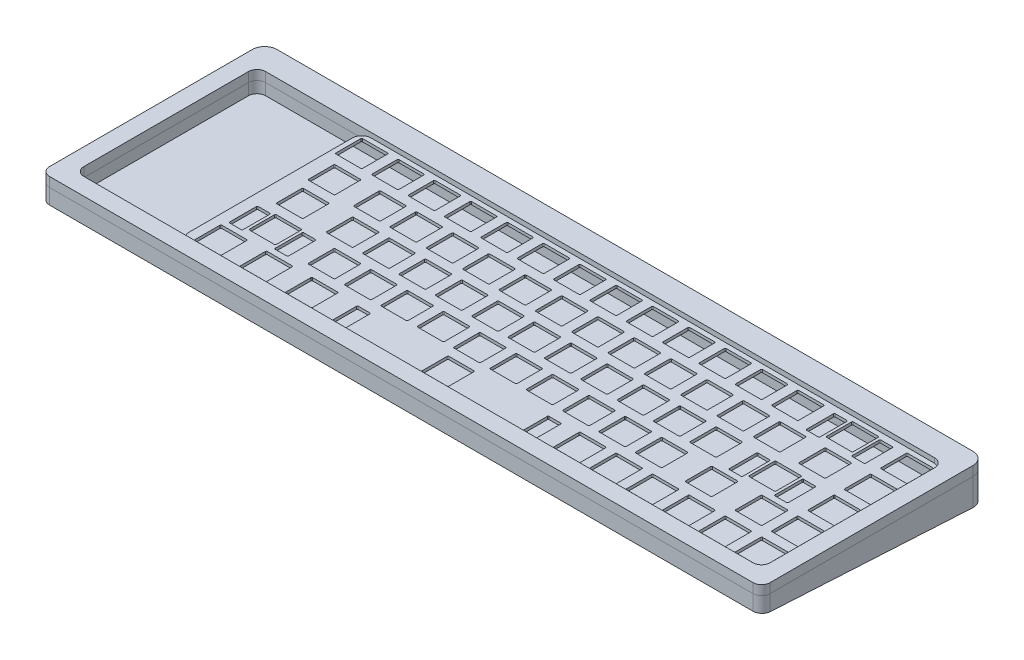
SolidWorks part; units mm, degrees
other "PCB"
other "Plate"
other "Bottom"
other "Top"
ref_plane "Front Plane" through (0, 0, 0) normal (0, 0, 1) x (1, 0, 0)
ref_plane "Top Plane" through (0, 0, 0) normal (0, 1, 0) x (1, 0, 0)
ref_plane "Right Plane" through (0, 0, 0) normal (1, 0, 0) x (0, 0, -1)
sketch "Sketch1" plane through (0, 0, 0) normal (0, 1, 0) x (1, 0, 0)
  line L0 (-179.825, 47.6224) -> (-179.825, 47.625)
  line L1 (-179.8217, 47.625) -> (179.825, 47.625)
  line L2 (-179.825, 47.6224) -> (-179.825, -47.625)
  line L3 (-179.825, -47.625) -> (179.825, -47.625)
  line L4 (179.825, 47.625) -> (179.825, -47.625)
  line L5 (-179.825, 47.625) -> (179.825, -47.625) construction
  line L6 (-179.825, -47.625) -> (179.825, 47.625) construction
  line L7 (-179.825, 47.625) -> (-179.8217, 47.625)
  circle A4 centre (157.075, 19.175) radius 1.1
  circle A5 centre (136.925, -16.775) radius 1.1
  circle A6 centre (-153.475, 33.725) radius 1.1
  circle A7 centre (17.925, 22.275) radius 1.1
  circle A8 centre (17.875, -35.075) radius 1.1
  circle A9 centre (-130.375, -35.725) radius 1.1
  point P0 (0, 0)
  dimension "D4" = 2.2
  dimension "D7" = 2.2
  dimension "D8" = 2.2
  dimension "D9" = 2.2
  dimension "D10" = 2.2
  dimension "D11" = 2.2
  dimension "D1" = 359.65
  dimension "D2" = 95.25
  dimension "D5" = 22.75
  dimension "D6" = 28.45
  dimension "D12" = 42.9
  dimension "D13" = 30.85
  dimension "D14" = 25.35
  dimension "D15" = 161.9
  dimension "D16" = 12.55
  dimension "D17" = 161.95
  dimension "D18" = 11.9
  dimension "D19" = 49.45
  dimension "D20" = 13.9
  dimension "D21" = 26.35
sketch "Sketch2" plane through (0, 0, 0) normal (0, 1, 0) x (1, 0, 0)
  line L0 (-188.825, 54.625) -> (-188.825, 60.625)
  line L1 (-188.825, 60.625) -> (-182.825, 60.625)
  line L4 (-179.825, 46.625) -> (-179.825, -46.625)
  line L5 (-178.825, -47.625) -> (178.825, -47.625)
  line L6 (179.825, 46.625) -> (179.825, -46.625)
  line L7 (-178.825, 47.625) -> (178.825, 47.625)
  line L8 (-179.825, 46.625) -> (-179.825, 47.625)
  line L9 (-182.825, 60.625) -> (188.825, 60.625)
  line L10 (-188.825, 54.625) -> (-188.825, -56.625)
  line L11 (-188.825, -56.625) -> (188.825, -56.625)
  line L12 (188.825, 60.625) -> (188.825, -56.625)
  line L13 (-179.825, 47.625) -> (-178.825, 47.625)
  line L14 (-179.825, -46.625) -> (-179.825, -47.625)
  line L15 (-179.825, -47.625) -> (-178.825, -47.625)
  line L16 (178.825, -47.625) -> (179.825, -47.625)
  line L17 (179.825, -47.625) -> (179.825, -46.625)
  line L18 (178.825, 47.625) -> (179.825, 47.625)
  line L19 (179.825, 47.625) -> (179.825, 46.625)
  circle A0 centre (157.075, 19.175) radius 1.1 construction
  circle A1 centre (136.925, -16.775) radius 1.1 construction
  circle A2 centre (17.875, -35.075) radius 1.1 construction
  circle A3 centre (17.925, 22.275) radius 1.1 construction
  circle A4 centre (-153.475, 33.725) radius 1.1 construction
  circle A5 centre (-130.375, -35.725) radius 1.1 construction
  circle A10 centre (157.075, 19.175) radius 1.1
  circle A11 centre (136.925, -16.775) radius 1.1
  circle A12 centre (17.875, -35.075) radius 1.1
  circle A13 centre (17.925, 22.275) radius 1.1
  circle A14 centre (-153.475, 33.725) radius 1.1
  circle A15 centre (-130.375, -35.725) radius 1.1
  point P30 (0, 0)
  dimension "D1" = 13
  dimension "D2" = 9
  dimension "D3" = 9
  dimension "D4" = 9
extrude "Boss-Extrude1" add sketch "Sketch2" along normal blind 13
sketch "Sketch4" plane through (0, 0, 0) normal (0, -1, 0) x (1, 0, 0)
  line L1 (-188.825, -60.625) -> (188.825, -60.625) construction
  line L3 (-188.825, 56.625) -> (188.825, 56.625) construction
  line L4 (-179.825, 47.625) -> (-179.825, -47.625)
  line L5 (179.825, 47.625) -> (-179.825, 47.625)
  line L6 (179.825, -47.625) -> (179.825, 47.625)
  line L7 (-179.825, -47.625) -> (179.825, -47.625)
  line L8 (-179.825, 47.625) -> (-179.825, -47.625)
  line L10 (179.825, -47.625) -> (179.825, 47.625)
  line L11 (-179.825, -47.625) -> (179.825, -47.625)
  line L12 (188.825, -60.625) -> (188.825, 56.625)
  line L13 (-188.825, -60.625) -> (188.825, -60.625)
  line L14 (-188.825, -60.625) -> (-188.825, 56.625)
  line L15 (-188.825, 56.625) -> (188.825, 56.625)
  line M10 (-179.825, -47.625) -> (-179.825, 47.625)
  line M12 (-179.825, 47.625) -> (179.825, 47.625)
  line M14 (179.825, 47.625) -> (179.825, -47.625)
  line M16 (179.825, -47.625) -> (-179.825, -47.625)
  line M17 (-188.825, 56.625) -> (-188.825, -60.625)
  line M19 (-188.825, -60.625) -> (188.825, -60.625)
  line M21 (188.825, -60.625) -> (188.825, 56.625)
  line M23 (188.825, 56.625) -> (-188.825, 56.625)
  dimension "D1" = 0
extrude "Boss-Extrude3" add sketch "Sketch4" along normal blind 10.5 contours M17 M19 M21 M23 M16 M10 M12 M14 | M16 M14 M12 M10 region at (0, 0, 0) region at (0, 0, -56.6707)
sketch "Sketch12" plane through (-188.825, 0, 0) normal (-1, 0, 0) x (0, 0, 1)
  line L0 (-60.625, 0) -> (56.625, 0) construction
  line L1 (-60.625, 13) -> (-60.625, -10.5) construction
  line L2 (56.625, 13) -> (56.625, -10.5) construction
  line L3 (56.625, -10.5) -> (-60.625, -10.5) construction
  line L4 (-60.625, -10.5) -> (-60.625, -6.5)
  line L5 (-60.625, -6.5) -> (56.625, 0)
  line L6 (56.625, 0) -> (56.625, -10.5)
  line L7 (56.625, -10.5) -> (-60.625, -10.5)
  dimension "D1" = 10.5
  dimension "D2" = 4
extrude "Cut-Extrude3" cut sketch "Sketch12" against normal blind 400
sketch "Sketch9" plane through (0, 0, 0) normal (0, 1, 0) x (1, 0, 0)
  line L0 (-121.9453, 45.1) -> (-108.9453, 45.1)
  line L1 (-121.9453, 31.1) -> (-108.9453, 31.1)
  line L2 (-122.4453, 44.6) -> (-122.4453, 31.6)
  line L3 (-108.4453, 44.6) -> (-108.4453, 31.6)
  line L4 (-102.8953, 45.1) -> (-89.8953, 45.1)
  line L5 (-102.8953, 31.1) -> (-89.8953, 31.1)
  line L6 (-103.3953, 44.6) -> (-103.3953, 31.6)
  line L7 (-89.3953, 44.6) -> (-89.3953, 31.6)
  line L8 (-83.8453, 45.1) -> (-70.8453, 45.1)
  line L9 (-83.8453, 31.1) -> (-70.8453, 31.1)
  line L10 (-84.3453, 44.6) -> (-84.3453, 31.6)
  line L11 (-70.3453, 44.6) -> (-70.3453, 31.6)
  line L12 (-64.7953, 45.1) -> (-51.7953, 45.1)
  line L13 (-64.7953, 31.1) -> (-51.7953, 31.1)
  line L14 (-65.2953, 44.6) -> (-65.2953, 31.6)
  line L15 (-51.2953, 44.6) -> (-51.2953, 31.6)
  line L16 (-45.7453, 45.1) -> (-32.7453, 45.1)
  line L17 (-45.7453, 31.1) -> (-32.7453, 31.1)
  line L18 (-46.2453, 44.6) -> (-46.2453, 31.6)
  line L19 (-32.2453, 44.6) -> (-32.2453, 31.6)
  line L20 (-26.6953, 45.1) -> (-13.6953, 45.1)
  line L21 (-26.6953, 31.1) -> (-13.6953, 31.1)
  line L22 (-27.1953, 44.6) -> (-27.1953, 31.6)
  line L23 (-13.1953, 44.6) -> (-13.1953, 31.6)
  line L24 (-7.6453, 45.1) -> (5.3547, 45.1)
  line L25 (-7.6453, 31.1) -> (5.3547, 31.1)
  line L26 (-8.1453, 44.6) -> (-8.1453, 31.6)
  line L27 (5.8547, 44.6) -> (5.8547, 31.6)
  line L28 (11.4047, 45.1) -> (24.4047, 45.1)
  line L29 (11.4047, 31.1) -> (24.4047, 31.1)
  line L30 (10.9047, 44.6) -> (10.9047, 31.6)
  line L31 (24.9047, 44.6) -> (24.9047, 31.6)
  line L32 (30.4547, 45.1) -> (43.4547, 45.1)
  line L33 (30.4547, 31.1) -> (43.4547, 31.1)
  line L34 (29.9547, 44.6) -> (29.9547, 31.6)
  line L35 (43.9547, 44.6) -> (43.9547, 31.6)
  line L36 (49.5047, 45.1) -> (62.5047, 45.1)
  line L37 (49.5047, 31.1) -> (62.5047, 31.1)
  line L38 (49.0047, 44.6) -> (49.0047, 31.6)
  line L39 (63.0047, 44.6) -> (63.0047, 31.6)
  line L40 (68.5547, 45.1) -> (81.5547, 45.1)
  line L41 (68.5547, 31.1) -> (81.5547, 31.1)
  line L42 (68.0547, 44.6) -> (68.0547, 31.6)
  line L43 (82.0547, 44.6) -> (82.0547, 31.6)
  line L44 (87.6047, 45.1) -> (100.6047, 45.1)
  line L45 (87.6047, 31.1) -> (100.6047, 31.1)
  line L46 (87.1047, 44.6) -> (87.1047, 31.6)
  line L47 (101.1047, 44.6) -> (101.1047, 31.6)
  line L48 (106.6547, 45.1) -> (119.6547, 45.1)
  line L49 (106.6547, 31.1) -> (119.6547, 31.1)
  line L50 (106.1547, 44.6) -> (106.1547, 31.6)
  line L51 (120.1547, 44.6) -> (120.1547, 31.6)
  line L52 (135.2297, 45.1) -> (148.2297, 45.1)
  line L53 (135.2297, 31.1) -> (148.2297, 31.1)
  line L54 (134.7297, 44.6) -> (134.7297, 31.6)
  line L55 (148.7297, 44.6) -> (148.7297, 31.6)
  line L56 (150.6677, 44.1) -> (156.6677, 44.1)
  line L57 (150.6677, 29.1) -> (156.6677, 29.1)
  line L58 (150.1677, 43.6) -> (150.1677, 29.6)
  line L59 (157.1677, 43.6) -> (157.1677, 29.6)
  line L60 (126.7917, 44.1) -> (132.7917, 44.1)
  line L61 (126.7917, 29.1) -> (132.7917, 29.1)
  line L62 (126.2917, 43.6) -> (126.2917, 29.6)
  line L63 (133.2917, 43.6) -> (133.2917, 29.6)
  line L64 (163.8047, 45.1) -> (176.8047, 45.1)
  line L65 (163.8047, 31.1) -> (176.8047, 31.1)
  line L66 (163.3047, 44.6) -> (163.3047, 31.6)
  line L67 (177.3047, 44.6) -> (177.3047, 31.6)
  line L68 (-117.1828, 26.05) -> (-104.1828, 26.05)
  line L69 (-117.1828, 12.05) -> (-104.1828, 12.05)
  line L70 (-117.6828, 25.55) -> (-117.6828, 12.55)
  line L71 (-103.6828, 25.55) -> (-103.6828, 12.55)
  line L72 (-93.3703, 26.05) -> (-80.3703, 26.05)
  line L73 (-93.3703, 12.05) -> (-80.3703, 12.05)
  line L74 (-93.8703, 25.55) -> (-93.8703, 12.55)
  line L75 (-79.8703, 25.55) -> (-79.8703, 12.55)
  line L76 (-74.3203, 26.05) -> (-61.3203, 26.05)
  line L77 (-74.3203, 12.05) -> (-61.3203, 12.05)
  line L78 (-74.8203, 25.55) -> (-74.8203, 12.55)
  line L79 (-60.8203, 25.55) -> (-60.8203, 12.55)
  line L80 (-55.2703, 26.05) -> (-42.2703, 26.05)
  line L81 (-55.2703, 12.05) -> (-42.2703, 12.05)
  line L82 (-55.7703, 25.55) -> (-55.7703, 12.55)
  line L83 (-41.7703, 25.55) -> (-41.7703, 12.55)
  line L84 (-36.2203, 26.05) -> (-23.2203, 26.05)
  line L85 (-36.2203, 12.05) -> (-23.2203, 12.05)
  line L86 (-36.7203, 25.55) -> (-36.7203, 12.55)
  line L87 (-22.7203, 25.55) -> (-22.7203, 12.55)
  line L88 (-17.1703, 26.05) -> (-4.1703, 26.05)
  line L89 (-17.1703, 12.05) -> (-4.1703, 12.05)
  line L90 (-17.6703, 25.55) -> (-17.6703, 12.55)
  line L91 (-3.6703, 25.55) -> (-3.6703, 12.55)
  line L92 (1.8797, 26.05) -> (14.8797, 26.05)
  line L93 (1.8797, 12.05) -> (14.8797, 12.05)
  line L94 (1.3797, 25.55) -> (1.3797, 12.55)
  line L95 (15.3797, 25.55) -> (15.3797, 12.55)
  line L96 (20.9297, 26.05) -> (33.9297, 26.05)
  line L97 (20.9297, 12.05) -> (33.9297, 12.05)
  line L98 (20.4297, 25.55) -> (20.4297, 12.55)
  line L99 (34.4297, 25.55) -> (34.4297, 12.55)
  line L100 (39.9797, 26.05) -> (52.9797, 26.05)
  line L101 (39.9797, 12.05) -> (52.9797, 12.05)
  line L102 (39.4797, 25.55) -> (39.4797, 12.55)
  line L103 (53.4797, 25.55) -> (53.4797, 12.55)
  line L104 (59.0297, 26.05) -> (72.0297, 26.05)
  line L105 (59.0297, 12.05) -> (72.0297, 12.05)
  line L106 (58.5297, 25.55) -> (58.5297, 12.55)
  line L107 (72.5297, 25.55) -> (72.5297, 12.55)
  line L108 (78.0797, 26.05) -> (91.0797, 26.05)
  line L109 (78.0797, 12.05) -> (91.0797, 12.05)
  line L110 (77.5797, 25.55) -> (77.5797, 12.55)
  line L111 (91.5797, 25.55) -> (91.5797, 12.55)
  line L112 (97.1297, 26.05) -> (110.1297, 26.05)
  line L113 (97.1297, 12.05) -> (110.1297, 12.05)
  line L114 (96.6297, 25.55) -> (96.6297, 12.55)
  line L115 (110.6297, 25.55) -> (110.6297, 12.55)
  line L116 (116.1797, 26.05) -> (129.1797, 26.05)
  line L117 (116.1797, 12.05) -> (129.1797, 12.05)
  line L118 (115.6797, 25.55) -> (115.6797, 12.55)
  line L119 (129.6797, 25.55) -> (129.6797, 12.55)
  line L120 (139.9922, 26.05) -> (152.9922, 26.05)
  line L121 (139.9922, 12.05) -> (152.9922, 12.05)
  line L122 (139.4922, 25.55) -> (139.4922, 12.55)
  line L123 (153.4922, 25.55) -> (153.4922, 12.55)
  line L124 (163.8047, 26.05) -> (176.8047, 26.05)
  line L125 (163.8047, 12.05) -> (176.8047, 12.05)
  line L126 (163.3047, 25.55) -> (163.3047, 12.55)
  line L127 (177.3047, 25.55) -> (177.3047, 12.55)
  line L128 (-114.8016, 7) -> (-101.8016, 7)
  line L129 (-114.8016, -7) -> (-101.8016, -7)
  line L130 (-115.3016, 6.5) -> (-115.3016, -6.5)
  line L131 (-101.3016, 6.5) -> (-101.3016, -6.5)
  line L132 (-88.6078, 7) -> (-75.6078, 7)
  line L133 (-88.6078, -7) -> (-75.6078, -7)
  line L134 (-89.1078, 6.5) -> (-89.1078, -6.5)
  line L135 (-75.1078, 6.5) -> (-75.1078, -6.5)
  line L136 (-69.5578, 7) -> (-56.5578, 7)
  line L137 (-69.5578, -7) -> (-56.5578, -7)
  line L138 (-70.0578, 6.5) -> (-70.0578, -6.5)
  line L139 (-56.0578, 6.5) -> (-56.0578, -6.5)
  line L140 (-50.5078, 7) -> (-37.5078, 7)
  line L141 (-50.5078, -7) -> (-37.5078, -7)
  line L142 (-51.0078, 6.5) -> (-51.0078, -6.5)
  line L143 (-37.0078, 6.5) -> (-37.0078, -6.5)
  line L144 (-31.4578, 7) -> (-18.4578, 7)
  line L145 (-31.4578, -7) -> (-18.4578, -7)
  line L146 (-31.9578, 6.5) -> (-31.9578, -6.5)
  line L147 (-17.9578, 6.5) -> (-17.9578, -6.5)
  line L148 (-12.4078, 7) -> (0.5922, 7)
  line L149 (-12.4078, -7) -> (0.5922, -7)
  line L150 (-12.9078, 6.5) -> (-12.9078, -6.5)
  line L151 (1.0922, 6.5) -> (1.0922, -6.5)
  line L152 (6.6422, 7) -> (19.6422, 7)
  line L153 (6.6422, -7) -> (19.6422, -7)
  line L154 (6.1422, 6.5) -> (6.1422, -6.5)
  line L155 (20.1422, 6.5) -> (20.1422, -6.5)
  line L156 (25.6922, 7) -> (38.6922, 7)
  line L157 (25.6922, -7) -> (38.6922, -7)
  line L158 (25.1922, 6.5) -> (25.1922, -6.5)
  line L159 (39.1922, 6.5) -> (39.1922, -6.5)
  line L160 (44.7422, 7) -> (57.7422, 7)
  line L161 (44.7422, -7) -> (57.7422, -7)
  line L162 (44.2422, 6.5) -> (44.2422, -6.5)
  line L163 (58.2422, 6.5) -> (58.2422, -6.5)
  line L164 (63.7922, 7) -> (76.7922, 7)
  line L165 (63.7922, -7) -> (76.7922, -7)
  line L166 (63.2922, 6.5) -> (63.2922, -6.5)
  line L167 (77.2922, 6.5) -> (77.2922, -6.5)
  line L168 (82.8422, 7) -> (95.8422, 7)
  line L169 (82.8422, -7) -> (95.8422, -7)
  line L170 (82.3422, 6.5) -> (82.3422, -6.5)
  line L171 (96.3422, 6.5) -> (96.3422, -6.5)
  line L172 (101.8922, 7) -> (114.8922, 7)
  line L173 (101.8922, -7) -> (114.8922, -7)
  line L174 (101.3922, 6.5) -> (101.3922, -6.5)
  line L175 (115.3922, 6.5) -> (115.3922, -6.5)
  line L176 (132.8484, 7) -> (145.8484, 7)
  line L177 (132.8484, -7) -> (145.8484, -7)
  line L178 (132.3484, 6.5) -> (132.3484, -6.5)
  line L179 (146.3484, 6.5) -> (146.3484, -6.5)
  line L180 (148.2864, 6) -> (154.2864, 6)
  line L181 (148.2864, -9) -> (154.2864, -9)
  line L182 (147.7864, 5.5) -> (147.7864, -8.5)
  line L183 (154.7864, 5.5) -> (154.7864, -8.5)
  line L184 (124.4104, 6) -> (130.4104, 6)
  line L185 (124.4104, -9) -> (130.4104, -9)
  line L186 (123.9104, 5.5) -> (123.9104, -8.5)
  line L187 (130.9104, 5.5) -> (130.9104, -8.5)
  line L188 (163.8047, 7) -> (176.8047, 7)
  line L189 (163.8047, -7) -> (176.8047, -7)
  line L190 (163.3047, 6.5) -> (163.3047, -6.5)
  line L191 (177.3047, 6.5) -> (177.3047, -6.5)
  line L192 (-110.0391, -12.05) -> (-97.0391, -12.05)
  line L193 (-110.0391, -26.05) -> (-97.0391, -26.05)
  line L194 (-110.5391, -12.55) -> (-110.5391, -25.55)
  line L195 (-96.5391, -12.55) -> (-96.5391, -25.55)
  line L196 (-94.6011, -13.05) -> (-88.6011, -13.05)
  line L197 (-94.6011, -28.05) -> (-88.6011, -28.05)
  line L198 (-95.1011, -13.55) -> (-95.1011, -27.55)
  line L199 (-88.1011, -13.55) -> (-88.1011, -27.55)
  line L200 (-118.4771, -13.05) -> (-112.4771, -13.05)
  line L201 (-118.4771, -28.05) -> (-112.4771, -28.05)
  line L202 (-118.9771, -13.55) -> (-118.9771, -27.55)
  line L203 (-111.9771, -13.55) -> (-111.9771, -27.55)
  line L204 (-79.0828, -12.05) -> (-66.0828, -12.05)
  line L205 (-79.0828, -26.05) -> (-66.0828, -26.05)
  line L206 (-79.5828, -12.55) -> (-79.5828, -25.55)
  line L207 (-65.5828, -12.55) -> (-65.5828, -25.55)
  line L208 (-60.0328, -12.05) -> (-47.0328, -12.05)
  line L209 (-60.0328, -26.05) -> (-47.0328, -26.05)
  line L210 (-60.5328, -12.55) -> (-60.5328, -25.55)
  line L211 (-46.5328, -12.55) -> (-46.5328, -25.55)
  line L212 (-40.9828, -12.05) -> (-27.9828, -12.05)
  line L213 (-40.9828, -26.05) -> (-27.9828, -26.05)
  line L214 (-41.4828, -12.55) -> (-41.4828, -25.55)
  line L215 (-27.4828, -12.55) -> (-27.4828, -25.55)
  line L216 (-21.9328, -12.05) -> (-8.9328, -12.05)
  line L217 (-21.9328, -26.05) -> (-8.9328, -26.05)
  line L218 (-22.4328, -12.55) -> (-22.4328, -25.55)
  line L219 (-8.4328, -12.55) -> (-8.4328, -25.55)
  line L220 (-2.8828, -12.05) -> (10.1172, -12.05)
  line L221 (-2.8828, -26.05) -> (10.1172, -26.05)
  line L222 (-3.3828, -12.55) -> (-3.3828, -25.55)
  line L223 (10.6172, -12.55) -> (10.6172, -25.55)
  line L224 (16.1672, -12.05) -> (29.1672, -12.05)
  line L225 (16.1672, -26.05) -> (29.1672, -26.05)
  line L226 (15.6672, -12.55) -> (15.6672, -25.55)
  line L227 (29.6672, -12.55) -> (29.6672, -25.55)
  line L228 (35.2172, -12.05) -> (48.2172, -12.05)
  line L229 (35.2172, -26.05) -> (48.2172, -26.05)
  line L230 (34.7172, -12.55) -> (34.7172, -25.55)
  line L231 (48.7172, -12.55) -> (48.7172, -25.55)
  line L232 (54.2672, -12.05) -> (67.2672, -12.05)
  line L233 (54.2672, -26.05) -> (67.2672, -26.05)
  line L234 (53.7672, -12.55) -> (53.7672, -25.55)
  line L235 (67.7672, -12.55) -> (67.7672, -25.55)
  line L236 (73.3172, -12.05) -> (86.3172, -12.05)
  line L237 (73.3172, -26.05) -> (86.3172, -26.05)
  line L238 (72.8172, -12.55) -> (72.8172, -25.55)
  line L239 (86.8172, -12.55) -> (86.8172, -25.55)
  line L240 (92.3672, -12.05) -> (105.3672, -12.05)
  line L241 (92.3672, -26.05) -> (105.3672, -26.05)
  line L242 (91.8672, -12.55) -> (91.8672, -25.55)
  line L243 (105.8672, -12.55) -> (105.8672, -25.55)
  line L244 (118.5609, -12.05) -> (131.5609, -12.05)
  line L245 (118.5609, -26.05) -> (131.5609, -26.05)
  line L246 (118.0609, -12.55) -> (118.0609, -25.55)
  line L247 (132.0609, -12.55) -> (132.0609, -25.55)
  line L248 (144.7547, -12.05) -> (157.7547, -12.05)
  line L249 (144.7547, -26.05) -> (157.7547, -26.05)
  line L250 (144.2547, -12.55) -> (144.2547, -25.55)
  line L251 (158.2547, -12.55) -> (158.2547, -25.55)
  line L252 (163.8047, -12.05) -> (176.8047, -12.05)
  line L253 (163.8047, -26.05) -> (176.8047, -26.05)
  line L254 (163.3047, -12.55) -> (163.3047, -25.55)
  line L255 (177.3047, -12.55) -> (177.3047, -25.55)
  line L256 (-119.5641, -31.1) -> (-106.5641, -31.1)
  line L257 (-119.5641, -45.1) -> (-106.5641, -45.1)
  line L258 (-120.0641, -31.6) -> (-120.0641, -44.6)
  line L259 (-106.0641, -31.6) -> (-106.0641, -44.6)
  line L260 (-95.7516, -31.1) -> (-82.7516, -31.1)
  line L261 (-95.7516, -45.1) -> (-82.7516, -45.1)
  line L262 (-96.2516, -31.6) -> (-96.2516, -44.6)
  line L263 (-82.2516, -31.6) -> (-82.2516, -44.6)
  line L264 (-71.9391, -31.1) -> (-58.9391, -31.1)
  line L265 (-71.9391, -45.1) -> (-58.9391, -45.1)
  line L266 (-72.4391, -31.6) -> (-72.4391, -44.6)
  line L267 (-58.4391, -31.6) -> (-58.4391, -44.6)
  line L268 (-0.5016, -31.1) -> (12.4984, -31.1)
  line L269 (-0.5016, -45.1) -> (12.4984, -45.1)
  line L270 (-1.0016, -31.6) -> (-1.0016, -44.6)
  line L271 (12.9984, -31.6) -> (12.9984, -44.6)
  line L272 (52.9984, -32.1) -> (58.9984, -32.1)
  line L273 (52.9984, -47.1) -> (58.9984, -47.1)
  line L274 (52.4984, -32.6) -> (52.4984, -46.6)
  line L275 (59.4984, -32.6) -> (59.4984, -46.6)
  line L276 (-47.0016, -32.1) -> (-41.0016, -32.1)
  line L277 (-47.0016, -47.1) -> (-41.0016, -47.1)
  line L278 (-47.5016, -32.6) -> (-47.5016, -46.6)
  line L279 (-40.5016, -32.6) -> (-40.5016, -46.6)
  line L280 (68.5547, -31.1) -> (81.5547, -31.1)
  line L281 (68.5547, -45.1) -> (81.5547, -45.1)
  line L282 (68.0547, -31.6) -> (68.0547, -44.6)
  line L283 (82.0547, -31.6) -> (82.0547, -44.6)
  line L284 (87.6047, -31.1) -> (100.6047, -31.1)
  line L285 (87.6047, -45.1) -> (100.6047, -45.1)
  line L286 (87.1047, -31.6) -> (87.1047, -44.6)
  line L287 (101.1047, -31.6) -> (101.1047, -44.6)
  line L288 (106.6547, -31.1) -> (119.6547, -31.1)
  line L289 (106.6547, -45.1) -> (119.6547, -45.1)
  line L290 (106.1547, -31.6) -> (106.1547, -44.6)
  line L291 (120.1547, -31.6) -> (120.1547, -44.6)
  line L292 (125.7047, -31.1) -> (138.7047, -31.1)
  line L293 (125.7047, -45.1) -> (138.7047, -45.1)
  line L294 (125.2047, -31.6) -> (125.2047, -44.6)
  line L295 (139.2047, -31.6) -> (139.2047, -44.6)
  line L296 (144.7547, -31.1) -> (157.7547, -31.1)
  line L297 (144.7547, -45.1) -> (157.7547, -45.1)
  line L298 (144.2547, -31.6) -> (144.2547, -44.6)
  line L299 (158.2547, -31.6) -> (158.2547, -44.6)
  line L300 (163.8047, -31.1) -> (176.8047, -31.1)
  line L301 (163.8047, -45.1) -> (176.8047, -45.1)
  line L302 (163.3047, -31.6) -> (163.3047, -44.6)
  line L303 (177.3047, -31.6) -> (177.3047, -44.6)
  line L304 (-119.9703, 47.625) -> (-103.2456, 47.625)
  line L305 (-119.9703, -47.625) -> (-100.699, -47.625)
  line L306 (-124.9703, 42.625) -> (-124.9703, -42.625)
  line L307 (179.8297, 42.625) -> (179.8297, 7.5)
  line L308 (-103.2456, 53.125) -> (-103.2456, 47.625)
  line L309 (-124.9703, 47.625) -> (-103.2456, 47.625)
  line L311 (-101.2456, 55.125) -> (-90.2456, 55.125)
  line L312 (-88.2456, 47.625) -> (-88.2456, 53.125)
  line L313 (-23.2456, 53.125) -> (-23.2456, 47.625)
  line L314 (-21.2456, 55.125) -> (-10.2456, 55.125)
  line L315 (-8.2456, 47.625) -> (-8.2456, 53.125)
  line L316 (56.7544, 53.125) -> (56.7544, 47.625)
  line L317 (58.7544, 55.125) -> (69.7544, 55.125)
  line L318 (71.7544, 47.625) -> (71.7544, 53.125)
  line L319 (136.7544, 53.125) -> (136.7544, 47.625)
  line L320 (138.7544, 55.125) -> (149.7544, 55.125)
  line L321 (151.7544, 47.625) -> (151.7544, 53.125)
  line L322 (-88.2456, 47.625) -> (-23.2456, 47.625)
  line L323 (-8.2456, 47.625) -> (56.7544, 47.625)
  line L324 (71.7544, 47.625) -> (136.7544, 47.625)
  line L325 (151.7544, 47.625) -> (174.8297, 47.625)
  line L326 (-20.699, -47.625) -> (-20.699, -52.625)
  line L327 (-5.699, -47.625) -> (-5.699, -52.625)
  line L329 (-100.699, -47.625) -> (-100.699, -52.625)
  line L330 (-98.699, -54.625) -> (-87.699, -54.625)
  line L331 (-85.699, -47.625) -> (-85.699, -52.625)
  line L332 (-18.699, -54.625) -> (-7.699, -54.625)
  line L333 (59.301, -47.625) -> (59.301, -52.625)
  line L334 (74.301, -47.625) -> (74.301, -52.625)
  line L335 (61.301, -54.625) -> (72.301, -54.625)
  line L336 (139.301, -47.625) -> (139.301, -52.625)
  line L337 (154.301, -47.625) -> (154.301, -52.625)
  line L338 (141.301, -54.625) -> (152.301, -54.625)
  line L339 (-85.699, -47.625) -> (-20.699, -47.625)
  line L340 (-5.699, -47.625) -> (59.301, -47.625)
  line L341 (74.301, -47.625) -> (139.301, -47.625)
  line L342 (154.301, -47.625) -> (174.8297, -47.625)
  line L343 (179.8297, -7.5) -> (179.8297, -42.625)
  line L348 (179.8297, 7.5) -> (179.8297, -7.5)
  arc A0 (-121.9453, 45.1) -> (-122.4453, 44.6) centre (-121.9453, 44.6) ccw
  arc A1 (-108.4453, 44.6) -> (-108.9453, 45.1) centre (-108.9453, 44.6) ccw
  arc A2 (-122.4453, 31.6) -> (-121.9453, 31.1) centre (-121.9453, 31.6) ccw
  arc A3 (-108.9453, 31.1) -> (-108.4453, 31.6) centre (-108.9453, 31.6) ccw
  arc A4 (-102.8953, 45.1) -> (-103.3953, 44.6) centre (-102.8953, 44.6) ccw
  arc A5 (-89.3953, 44.6) -> (-89.8953, 45.1) centre (-89.8953, 44.6) ccw
  arc A6 (-103.3953, 31.6) -> (-102.8953, 31.1) centre (-102.8953, 31.6) ccw
  arc A7 (-89.8953, 31.1) -> (-89.3953, 31.6) centre (-89.8953, 31.6) ccw
  arc A8 (-83.8453, 45.1) -> (-84.3453, 44.6) centre (-83.8453, 44.6) ccw
  arc A9 (-70.3453, 44.6) -> (-70.8453, 45.1) centre (-70.8453, 44.6) ccw
  arc A10 (-84.3453, 31.6) -> (-83.8453, 31.1) centre (-83.8453, 31.6) ccw
  arc A11 (-70.8453, 31.1) -> (-70.3453, 31.6) centre (-70.8453, 31.6) ccw
  arc A12 (-64.7953, 45.1) -> (-65.2953, 44.6) centre (-64.7953, 44.6) ccw
  arc A13 (-51.2953, 44.6) -> (-51.7953, 45.1) centre (-51.7953, 44.6) ccw
  arc A14 (-65.2953, 31.6) -> (-64.7953, 31.1) centre (-64.7953, 31.6) ccw
  arc A15 (-51.7953, 31.1) -> (-51.2953, 31.6) centre (-51.7953, 31.6) ccw
  arc A16 (-45.7453, 45.1) -> (-46.2453, 44.6) centre (-45.7453, 44.6) ccw
  arc A17 (-32.2453, 44.6) -> (-32.7453, 45.1) centre (-32.7453, 44.6) ccw
  arc A18 (-46.2453, 31.6) -> (-45.7453, 31.1) centre (-45.7453, 31.6) ccw
  arc A19 (-32.7453, 31.1) -> (-32.2453, 31.6) centre (-32.7453, 31.6) ccw
  arc A20 (-26.6953, 45.1) -> (-27.1953, 44.6) centre (-26.6953, 44.6) ccw
  arc A21 (-13.1953, 44.6) -> (-13.6953, 45.1) centre (-13.6953, 44.6) ccw
  arc A22 (-27.1953, 31.6) -> (-26.6953, 31.1) centre (-26.6953, 31.6) ccw
  arc A23 (-13.6953, 31.1) -> (-13.1953, 31.6) centre (-13.6953, 31.6) ccw
  arc A24 (-7.6453, 45.1) -> (-8.1453, 44.6) centre (-7.6453, 44.6) ccw
  arc A25 (5.8547, 44.6) -> (5.3547, 45.1) centre (5.3547, 44.6) ccw
  arc A26 (-8.1453, 31.6) -> (-7.6453, 31.1) centre (-7.6453, 31.6) ccw
  arc A27 (5.3547, 31.1) -> (5.8547, 31.6) centre (5.3547, 31.6) ccw
  arc A28 (11.4047, 45.1) -> (10.9047, 44.6) centre (11.4047, 44.6) ccw
  arc A29 (24.9047, 44.6) -> (24.4047, 45.1) centre (24.4047, 44.6) ccw
  arc A30 (10.9047, 31.6) -> (11.4047, 31.1) centre (11.4047, 31.6) ccw
  arc A31 (24.4047, 31.1) -> (24.9047, 31.6) centre (24.4047, 31.6) ccw
  arc A32 (30.4547, 45.1) -> (29.9547, 44.6) centre (30.4547, 44.6) ccw
  arc A33 (43.9547, 44.6) -> (43.4547, 45.1) centre (43.4547, 44.6) ccw
  arc A34 (29.9547, 31.6) -> (30.4547, 31.1) centre (30.4547, 31.6) ccw
  arc A35 (43.4547, 31.1) -> (43.9547, 31.6) centre (43.4547, 31.6) ccw
  arc A36 (49.5047, 45.1) -> (49.0047, 44.6) centre (49.5047, 44.6) ccw
  arc A37 (63.0047, 44.6) -> (62.5047, 45.1) centre (62.5047, 44.6) ccw
  arc A38 (49.0047, 31.6) -> (49.5047, 31.1) centre (49.5047, 31.6) ccw
  arc A39 (62.5047, 31.1) -> (63.0047, 31.6) centre (62.5047, 31.6) ccw
  arc A40 (68.5547, 45.1) -> (68.0547, 44.6) centre (68.5547, 44.6) ccw
  arc A41 (82.0547, 44.6) -> (81.5547, 45.1) centre (81.5547, 44.6) ccw
  arc A42 (68.0547, 31.6) -> (68.5547, 31.1) centre (68.5547, 31.6) ccw
  arc A43 (81.5547, 31.1) -> (82.0547, 31.6) centre (81.5547, 31.6) ccw
  arc A44 (87.6047, 45.1) -> (87.1047, 44.6) centre (87.6047, 44.6) ccw
  arc A45 (101.1047, 44.6) -> (100.6047, 45.1) centre (100.6047, 44.6) ccw
  arc A46 (87.1047, 31.6) -> (87.6047, 31.1) centre (87.6047, 31.6) ccw
  arc A47 (100.6047, 31.1) -> (101.1047, 31.6) centre (100.6047, 31.6) ccw
  arc A48 (106.6547, 45.1) -> (106.1547, 44.6) centre (106.6547, 44.6) ccw
  arc A49 (120.1547, 44.6) -> (119.6547, 45.1) centre (119.6547, 44.6) ccw
  arc A50 (106.1547, 31.6) -> (106.6547, 31.1) centre (106.6547, 31.6) ccw
  arc A51 (119.6547, 31.1) -> (120.1547, 31.6) centre (119.6547, 31.6) ccw
  arc A52 (135.2297, 45.1) -> (134.7297, 44.6) centre (135.2297, 44.6) ccw
  arc A53 (148.7297, 44.6) -> (148.2297, 45.1) centre (148.2297, 44.6) ccw
  arc A54 (134.7297, 31.6) -> (135.2297, 31.1) centre (135.2297, 31.6) ccw
  arc A55 (148.2297, 31.1) -> (148.7297, 31.6) centre (148.2297, 31.6) ccw
  arc A56 (150.6677, 44.1) -> (150.1677, 43.6) centre (150.6677, 43.6) ccw
  arc A57 (157.1677, 43.6) -> (156.6677, 44.1) centre (156.6677, 43.6) ccw
  arc A58 (150.1677, 29.6) -> (150.6677, 29.1) centre (150.6677, 29.6) ccw
  arc A59 (156.6677, 29.1) -> (157.1677, 29.6) centre (156.6677, 29.6) ccw
  arc A60 (126.7917, 44.1) -> (126.2917, 43.6) centre (126.7917, 43.6) ccw
  arc A61 (133.2917, 43.6) -> (132.7917, 44.1) centre (132.7917, 43.6) ccw
  arc A62 (126.2917, 29.6) -> (126.7917, 29.1) centre (126.7917, 29.6) ccw
  arc A63 (132.7917, 29.1) -> (133.2917, 29.6) centre (132.7917, 29.6) ccw
  arc A64 (163.8047, 45.1) -> (163.3047, 44.6) centre (163.8047, 44.6) ccw
  arc A65 (177.3047, 44.6) -> (176.8047, 45.1) centre (176.8047, 44.6) ccw
  arc A66 (163.3047, 31.6) -> (163.8047, 31.1) centre (163.8047, 31.6) ccw
  arc A67 (176.8047, 31.1) -> (177.3047, 31.6) centre (176.8047, 31.6) ccw
  arc A68 (-117.1828, 26.05) -> (-117.6828, 25.55) centre (-117.1828, 25.55) ccw
  arc A69 (-103.6828, 25.55) -> (-104.1828, 26.05) centre (-104.1828, 25.55) ccw
  arc A70 (-117.6828, 12.55) -> (-117.1828, 12.05) centre (-117.1828, 12.55) ccw
  arc A71 (-104.1828, 12.05) -> (-103.6828, 12.55) centre (-104.1828, 12.55) ccw
  arc A72 (-93.3703, 26.05) -> (-93.8703, 25.55) centre (-93.3703, 25.55) ccw
  arc A73 (-79.8703, 25.55) -> (-80.3703, 26.05) centre (-80.3703, 25.55) ccw
  arc A74 (-93.8703, 12.55) -> (-93.3703, 12.05) centre (-93.3703, 12.55) ccw
  arc A75 (-80.3703, 12.05) -> (-79.8703, 12.55) centre (-80.3703, 12.55) ccw
  arc A76 (-74.3203, 26.05) -> (-74.8203, 25.55) centre (-74.3203, 25.55) ccw
  arc A77 (-60.8203, 25.55) -> (-61.3203, 26.05) centre (-61.3203, 25.55) ccw
  arc A78 (-74.8203, 12.55) -> (-74.3203, 12.05) centre (-74.3203, 12.55) ccw
  arc A79 (-61.3203, 12.05) -> (-60.8203, 12.55) centre (-61.3203, 12.55) ccw
  arc A80 (-55.2703, 26.05) -> (-55.7703, 25.55) centre (-55.2703, 25.55) ccw
  arc A81 (-41.7703, 25.55) -> (-42.2703, 26.05) centre (-42.2703, 25.55) ccw
  arc A82 (-55.7703, 12.55) -> (-55.2703, 12.05) centre (-55.2703, 12.55) ccw
  arc A83 (-42.2703, 12.05) -> (-41.7703, 12.55) centre (-42.2703, 12.55) ccw
  arc A84 (-36.2203, 26.05) -> (-36.7203, 25.55) centre (-36.2203, 25.55) ccw
  arc A85 (-22.7203, 25.55) -> (-23.2203, 26.05) centre (-23.2203, 25.55) ccw
  arc A86 (-36.7203, 12.55) -> (-36.2203, 12.05) centre (-36.2203, 12.55) ccw
  arc A87 (-23.2203, 12.05) -> (-22.7203, 12.55) centre (-23.2203, 12.55) ccw
  arc A88 (-17.1703, 26.05) -> (-17.6703, 25.55) centre (-17.1703, 25.55) ccw
  arc A89 (-3.6703, 25.55) -> (-4.1703, 26.05) centre (-4.1703, 25.55) ccw
  arc A90 (-17.6703, 12.55) -> (-17.1703, 12.05) centre (-17.1703, 12.55) ccw
  arc A91 (-4.1703, 12.05) -> (-3.6703, 12.55) centre (-4.1703, 12.55) ccw
  arc A92 (1.8797, 26.05) -> (1.3797, 25.55) centre (1.8797, 25.55) ccw
  arc A93 (15.3797, 25.55) -> (14.8797, 26.05) centre (14.8797, 25.55) ccw
  arc A94 (1.3797, 12.55) -> (1.8797, 12.05) centre (1.8797, 12.55) ccw
  arc A95 (14.8797, 12.05) -> (15.3797, 12.55) centre (14.8797, 12.55) ccw
  arc A96 (20.9297, 26.05) -> (20.4297, 25.55) centre (20.9297, 25.55) ccw
  arc A97 (34.4297, 25.55) -> (33.9297, 26.05) centre (33.9297, 25.55) ccw
  arc A98 (20.4297, 12.55) -> (20.9297, 12.05) centre (20.9297, 12.55) ccw
  arc A99 (33.9297, 12.05) -> (34.4297, 12.55) centre (33.9297, 12.55) ccw
  arc A100 (39.9797, 26.05) -> (39.4797, 25.55) centre (39.9797, 25.55) ccw
  arc A101 (53.4797, 25.55) -> (52.9797, 26.05) centre (52.9797, 25.55) ccw
  arc A102 (39.4797, 12.55) -> (39.9797, 12.05) centre (39.9797, 12.55) ccw
  arc A103 (52.9797, 12.05) -> (53.4797, 12.55) centre (52.9797, 12.55) ccw
  arc A104 (59.0297, 26.05) -> (58.5297, 25.55) centre (59.0297, 25.55) ccw
  arc A105 (72.5297, 25.55) -> (72.0297, 26.05) centre (72.0297, 25.55) ccw
  arc A106 (58.5297, 12.55) -> (59.0297, 12.05) centre (59.0297, 12.55) ccw
  arc A107 (72.0297, 12.05) -> (72.5297, 12.55) centre (72.0297, 12.55) ccw
  arc A108 (78.0797, 26.05) -> (77.5797, 25.55) centre (78.0797, 25.55) ccw
  arc A109 (91.5797, 25.55) -> (91.0797, 26.05) centre (91.0797, 25.55) ccw
  arc A110 (77.5797, 12.55) -> (78.0797, 12.05) centre (78.0797, 12.55) ccw
  arc A111 (91.0797, 12.05) -> (91.5797, 12.55) centre (91.0797, 12.55) ccw
  arc A112 (97.1297, 26.05) -> (96.6297, 25.55) centre (97.1297, 25.55) ccw
  arc A113 (110.6297, 25.55) -> (110.1297, 26.05) centre (110.1297, 25.55) ccw
  arc A114 (96.6297, 12.55) -> (97.1297, 12.05) centre (97.1297, 12.55) ccw
  arc A115 (110.1297, 12.05) -> (110.6297, 12.55) centre (110.1297, 12.55) ccw
  arc A116 (116.1797, 26.05) -> (115.6797, 25.55) centre (116.1797, 25.55) ccw
  arc A117 (129.6797, 25.55) -> (129.1797, 26.05) centre (129.1797, 25.55) ccw
  arc A118 (115.6797, 12.55) -> (116.1797, 12.05) centre (116.1797, 12.55) ccw
  arc A119 (129.1797, 12.05) -> (129.6797, 12.55) centre (129.1797, 12.55) ccw
  arc A120 (139.9922, 26.05) -> (139.4922, 25.55) centre (139.9922, 25.55) ccw
  arc A121 (153.4922, 25.55) -> (152.9922, 26.05) centre (152.9922, 25.55) ccw
  arc A122 (139.4922, 12.55) -> (139.9922, 12.05) centre (139.9922, 12.55) ccw
  arc A123 (152.9922, 12.05) -> (153.4922, 12.55) centre (152.9922, 12.55) ccw
  arc A124 (163.8047, 26.05) -> (163.3047, 25.55) centre (163.8047, 25.55) ccw
  arc A125 (177.3047, 25.55) -> (176.8047, 26.05) centre (176.8047, 25.55) ccw
  arc A126 (163.3047, 12.55) -> (163.8047, 12.05) centre (163.8047, 12.55) ccw
  arc A127 (176.8047, 12.05) -> (177.3047, 12.55) centre (176.8047, 12.55) ccw
  arc A128 (-114.8016, 7) -> (-115.3016, 6.5) centre (-114.8016, 6.5) ccw
  arc A129 (-101.3016, 6.5) -> (-101.8016, 7) centre (-101.8016, 6.5) ccw
  arc A130 (-115.3016, -6.5) -> (-114.8016, -7) centre (-114.8016, -6.5) ccw
  arc A131 (-101.8016, -7) -> (-101.3016, -6.5) centre (-101.8016, -6.5) ccw
  arc A132 (-88.6078, 7) -> (-89.1078, 6.5) centre (-88.6078, 6.5) ccw
  arc A133 (-75.1078, 6.5) -> (-75.6078, 7) centre (-75.6078, 6.5) ccw
  arc A134 (-89.1078, -6.5) -> (-88.6078, -7) centre (-88.6078, -6.5) ccw
  arc A135 (-75.6078, -7) -> (-75.1078, -6.5) centre (-75.6078, -6.5) ccw
  arc A136 (-69.5578, 7) -> (-70.0578, 6.5) centre (-69.5578, 6.5) ccw
  arc A137 (-56.0578, 6.5) -> (-56.5578, 7) centre (-56.5578, 6.5) ccw
  arc A138 (-70.0578, -6.5) -> (-69.5578, -7) centre (-69.5578, -6.5) ccw
  arc A139 (-56.5578, -7) -> (-56.0578, -6.5) centre (-56.5578, -6.5) ccw
  arc A140 (-50.5078, 7) -> (-51.0078, 6.5) centre (-50.5078, 6.5) ccw
  arc A141 (-37.0078, 6.5) -> (-37.5078, 7) centre (-37.5078, 6.5) ccw
  arc A142 (-51.0078, -6.5) -> (-50.5078, -7) centre (-50.5078, -6.5) ccw
  arc A143 (-37.5078, -7) -> (-37.0078, -6.5) centre (-37.5078, -6.5) ccw
  arc A144 (-31.4578, 7) -> (-31.9578, 6.5) centre (-31.4578, 6.5) ccw
  arc A145 (-17.9578, 6.5) -> (-18.4578, 7) centre (-18.4578, 6.5) ccw
  arc A146 (-31.9578, -6.5) -> (-31.4578, -7) centre (-31.4578, -6.5) ccw
  arc A147 (-18.4578, -7) -> (-17.9578, -6.5) centre (-18.4578, -6.5) ccw
  arc A148 (-12.4078, 7) -> (-12.9078, 6.5) centre (-12.4078, 6.5) ccw
  arc A149 (1.0922, 6.5) -> (0.5922, 7) centre (0.5922, 6.5) ccw
  arc A150 (-12.9078, -6.5) -> (-12.4078, -7) centre (-12.4078, -6.5) ccw
  arc A151 (0.5922, -7) -> (1.0922, -6.5) centre (0.5922, -6.5) ccw
  arc A152 (6.6422, 7) -> (6.1422, 6.5) centre (6.6422, 6.5) ccw
  arc A153 (20.1422, 6.5) -> (19.6422, 7) centre (19.6422, 6.5) ccw
  arc A154 (6.1422, -6.5) -> (6.6422, -7) centre (6.6422, -6.5) ccw
  arc A155 (19.6422, -7) -> (20.1422, -6.5) centre (19.6422, -6.5) ccw
  arc A156 (25.6922, 7) -> (25.1922, 6.5) centre (25.6922, 6.5) ccw
  arc A157 (39.1922, 6.5) -> (38.6922, 7) centre (38.6922, 6.5) ccw
  arc A158 (25.1922, -6.5) -> (25.6922, -7) centre (25.6922, -6.5) ccw
  arc A159 (38.6922, -7) -> (39.1922, -6.5) centre (38.6922, -6.5) ccw
  arc A160 (44.7422, 7) -> (44.2422, 6.5) centre (44.7422, 6.5) ccw
  arc A161 (58.2422, 6.5) -> (57.7422, 7) centre (57.7422, 6.5) ccw
  arc A162 (44.2422, -6.5) -> (44.7422, -7) centre (44.7422, -6.5) ccw
  arc A163 (57.7422, -7) -> (58.2422, -6.5) centre (57.7422, -6.5) ccw
  arc A164 (63.7922, 7) -> (63.2922, 6.5) centre (63.7922, 6.5) ccw
  arc A165 (77.2922, 6.5) -> (76.7922, 7) centre (76.7922, 6.5) ccw
  arc A166 (63.2922, -6.5) -> (63.7922, -7) centre (63.7922, -6.5) ccw
  arc A167 (76.7922, -7) -> (77.2922, -6.5) centre (76.7922, -6.5) ccw
  arc A168 (82.8422, 7) -> (82.3422, 6.5) centre (82.8422, 6.5) ccw
  arc A169 (96.3422, 6.5) -> (95.8422, 7) centre (95.8422, 6.5) ccw
  arc A170 (82.3422, -6.5) -> (82.8422, -7) centre (82.8422, -6.5) ccw
  arc A171 (95.8422, -7) -> (96.3422, -6.5) centre (95.8422, -6.5) ccw
  arc A172 (101.8922, 7) -> (101.3922, 6.5) centre (101.8922, 6.5) ccw
  arc A173 (115.3922, 6.5) -> (114.8922, 7) centre (114.8922, 6.5) ccw
  arc A174 (101.3922, -6.5) -> (101.8922, -7) centre (101.8922, -6.5) ccw
  arc A175 (114.8922, -7) -> (115.3922, -6.5) centre (114.8922, -6.5) ccw
  arc A176 (132.8484, 7) -> (132.3484, 6.5) centre (132.8484, 6.5) ccw
  arc A177 (146.3484, 6.5) -> (145.8484, 7) centre (145.8484, 6.5) ccw
  arc A178 (132.3484, -6.5) -> (132.8484, -7) centre (132.8484, -6.5) ccw
  arc A179 (145.8484, -7) -> (146.3484, -6.5) centre (145.8484, -6.5) ccw
  arc A180 (148.2864, 6) -> (147.7864, 5.5) centre (148.2864, 5.5) ccw
  arc A181 (154.7864, 5.5) -> (154.2864, 6) centre (154.2864, 5.5) ccw
  arc A182 (147.7864, -8.5) -> (148.2864, -9) centre (148.2864, -8.5) ccw
  arc A183 (154.2864, -9) -> (154.7864, -8.5) centre (154.2864, -8.5) ccw
  arc A184 (124.4104, 6) -> (123.9104, 5.5) centre (124.4104, 5.5) ccw
  arc A185 (130.9104, 5.5) -> (130.4104, 6) centre (130.4104, 5.5) ccw
  arc A186 (123.9104, -8.5) -> (124.4104, -9) centre (124.4104, -8.5) ccw
  arc A187 (130.4104, -9) -> (130.9104, -8.5) centre (130.4104, -8.5) ccw
  arc A188 (163.8047, 7) -> (163.3047, 6.5) centre (163.8047, 6.5) ccw
  arc A189 (177.3047, 6.5) -> (176.8047, 7) centre (176.8047, 6.5) ccw
  arc A190 (163.3047, -6.5) -> (163.8047, -7) centre (163.8047, -6.5) ccw
  arc A191 (176.8047, -7) -> (177.3047, -6.5) centre (176.8047, -6.5) ccw
  arc A192 (-110.0391, -12.05) -> (-110.5391, -12.55) centre (-110.0391, -12.55) ccw
  arc A193 (-96.5391, -12.55) -> (-97.0391, -12.05) centre (-97.0391, -12.55) ccw
  arc A194 (-110.5391, -25.55) -> (-110.0391, -26.05) centre (-110.0391, -25.55) ccw
  arc A195 (-97.0391, -26.05) -> (-96.5391, -25.55) centre (-97.0391, -25.55) ccw
  arc A196 (-94.6011, -13.05) -> (-95.1011, -13.55) centre (-94.6011, -13.55) ccw
  arc A197 (-88.1011, -13.55) -> (-88.6011, -13.05) centre (-88.6011, -13.55) ccw
  arc A198 (-95.1011, -27.55) -> (-94.6011, -28.05) centre (-94.6011, -27.55) ccw
  arc A199 (-88.6011, -28.05) -> (-88.1011, -27.55) centre (-88.6011, -27.55) ccw
  arc A200 (-118.4771, -13.05) -> (-118.9771, -13.55) centre (-118.4771, -13.55) ccw
  arc A201 (-111.9771, -13.55) -> (-112.4771, -13.05) centre (-112.4771, -13.55) ccw
  arc A202 (-118.9771, -27.55) -> (-118.4771, -28.05) centre (-118.4771, -27.55) ccw
  arc A203 (-112.4771, -28.05) -> (-111.9771, -27.55) centre (-112.4771, -27.55) ccw
  arc A204 (-79.0828, -12.05) -> (-79.5828, -12.55) centre (-79.0828, -12.55) ccw
  arc A205 (-65.5828, -12.55) -> (-66.0828, -12.05) centre (-66.0828, -12.55) ccw
  arc A206 (-79.5828, -25.55) -> (-79.0828, -26.05) centre (-79.0828, -25.55) ccw
  arc A207 (-66.0828, -26.05) -> (-65.5828, -25.55) centre (-66.0828, -25.55) ccw
  arc A208 (-60.0328, -12.05) -> (-60.5328, -12.55) centre (-60.0328, -12.55) ccw
  arc A209 (-46.5328, -12.55) -> (-47.0328, -12.05) centre (-47.0328, -12.55) ccw
  arc A210 (-60.5328, -25.55) -> (-60.0328, -26.05) centre (-60.0328, -25.55) ccw
  arc A211 (-47.0328, -26.05) -> (-46.5328, -25.55) centre (-47.0328, -25.55) ccw
  arc A212 (-40.9828, -12.05) -> (-41.4828, -12.55) centre (-40.9828, -12.55) ccw
  arc A213 (-27.4828, -12.55) -> (-27.9828, -12.05) centre (-27.9828, -12.55) ccw
  arc A214 (-41.4828, -25.55) -> (-40.9828, -26.05) centre (-40.9828, -25.55) ccw
  arc A215 (-27.9828, -26.05) -> (-27.4828, -25.55) centre (-27.9828, -25.55) ccw
  arc A216 (-21.9328, -12.05) -> (-22.4328, -12.55) centre (-21.9328, -12.55) ccw
  arc A217 (-8.4328, -12.55) -> (-8.9328, -12.05) centre (-8.9328, -12.55) ccw
  arc A218 (-22.4328, -25.55) -> (-21.9328, -26.05) centre (-21.9328, -25.55) ccw
  arc A219 (-8.9328, -26.05) -> (-8.4328, -25.55) centre (-8.9328, -25.55) ccw
  arc A220 (-2.8828, -12.05) -> (-3.3828, -12.55) centre (-2.8828, -12.55) ccw
  arc A221 (10.6172, -12.55) -> (10.1172, -12.05) centre (10.1172, -12.55) ccw
  arc A222 (-3.3828, -25.55) -> (-2.8828, -26.05) centre (-2.8828, -25.55) ccw
  arc A223 (10.1172, -26.05) -> (10.6172, -25.55) centre (10.1172, -25.55) ccw
  arc A224 (16.1672, -12.05) -> (15.6672, -12.55) centre (16.1672, -12.55) ccw
  arc A225 (29.6672, -12.55) -> (29.1672, -12.05) centre (29.1672, -12.55) ccw
  arc A226 (15.6672, -25.55) -> (16.1672, -26.05) centre (16.1672, -25.55) ccw
  arc A227 (29.1672, -26.05) -> (29.6672, -25.55) centre (29.1672, -25.55) ccw
  arc A228 (35.2172, -12.05) -> (34.7172, -12.55) centre (35.2172, -12.55) ccw
  arc A229 (48.7172, -12.55) -> (48.2172, -12.05) centre (48.2172, -12.55) ccw
  arc A230 (34.7172, -25.55) -> (35.2172, -26.05) centre (35.2172, -25.55) ccw
  arc A231 (48.2172, -26.05) -> (48.7172, -25.55) centre (48.2172, -25.55) ccw
  arc A232 (54.2672, -12.05) -> (53.7672, -12.55) centre (54.2672, -12.55) ccw
  arc A233 (67.7672, -12.55) -> (67.2672, -12.05) centre (67.2672, -12.55) ccw
  arc A234 (53.7672, -25.55) -> (54.2672, -26.05) centre (54.2672, -25.55) ccw
  arc A235 (67.2672, -26.05) -> (67.7672, -25.55) centre (67.2672, -25.55) ccw
  arc A236 (73.3172, -12.05) -> (72.8172, -12.55) centre (73.3172, -12.55) ccw
  arc A237 (86.8172, -12.55) -> (86.3172, -12.05) centre (86.3172, -12.55) ccw
  arc A238 (72.8172, -25.55) -> (73.3172, -26.05) centre (73.3172, -25.55) ccw
  arc A239 (86.3172, -26.05) -> (86.8172, -25.55) centre (86.3172, -25.55) ccw
  arc A240 (92.3672, -12.05) -> (91.8672, -12.55) centre (92.3672, -12.55) ccw
  arc A241 (105.8672, -12.55) -> (105.3672, -12.05) centre (105.3672, -12.55) ccw
  arc A242 (91.8672, -25.55) -> (92.3672, -26.05) centre (92.3672, -25.55) ccw
  arc A243 (105.3672, -26.05) -> (105.8672, -25.55) centre (105.3672, -25.55) ccw
  arc A244 (118.5609, -12.05) -> (118.0609, -12.55) centre (118.5609, -12.55) ccw
  arc A245 (132.0609, -12.55) -> (131.5609, -12.05) centre (131.5609, -12.55) ccw
  arc A246 (118.0609, -25.55) -> (118.5609, -26.05) centre (118.5609, -25.55) ccw
  arc A247 (131.5609, -26.05) -> (132.0609, -25.55) centre (131.5609, -25.55) ccw
  arc A248 (144.7547, -12.05) -> (144.2547, -12.55) centre (144.7547, -12.55) ccw
  arc A249 (158.2547, -12.55) -> (157.7547, -12.05) centre (157.7547, -12.55) ccw
  arc A250 (144.2547, -25.55) -> (144.7547, -26.05) centre (144.7547, -25.55) ccw
  arc A251 (157.7547, -26.05) -> (158.2547, -25.55) centre (157.7547, -25.55) ccw
  arc A252 (163.8047, -12.05) -> (163.3047, -12.55) centre (163.8047, -12.55) ccw
  arc A253 (177.3047, -12.55) -> (176.8047, -12.05) centre (176.8047, -12.55) ccw
  arc A254 (163.3047, -25.55) -> (163.8047, -26.05) centre (163.8047, -25.55) ccw
  arc A255 (176.8047, -26.05) -> (177.3047, -25.55) centre (176.8047, -25.55) ccw
  arc A256 (-119.5641, -31.1) -> (-120.0641, -31.6) centre (-119.5641, -31.6) ccw
  arc A257 (-106.0641, -31.6) -> (-106.5641, -31.1) centre (-106.5641, -31.6) ccw
  arc A258 (-120.0641, -44.6) -> (-119.5641, -45.1) centre (-119.5641, -44.6) ccw
  arc A259 (-106.5641, -45.1) -> (-106.0641, -44.6) centre (-106.5641, -44.6) ccw
  arc A260 (-95.7516, -31.1) -> (-96.2516, -31.6) centre (-95.7516, -31.6) ccw
  arc A261 (-82.2516, -31.6) -> (-82.7516, -31.1) centre (-82.7516, -31.6) ccw
  arc A262 (-96.2516, -44.6) -> (-95.7516, -45.1) centre (-95.7516, -44.6) ccw
  arc A263 (-82.7516, -45.1) -> (-82.2516, -44.6) centre (-82.7516, -44.6) ccw
  arc A264 (-71.9391, -31.1) -> (-72.4391, -31.6) centre (-71.9391, -31.6) ccw
  arc A265 (-58.4391, -31.6) -> (-58.9391, -31.1) centre (-58.9391, -31.6) ccw
  arc A266 (-72.4391, -44.6) -> (-71.9391, -45.1) centre (-71.9391, -44.6) ccw
  arc A267 (-58.9391, -45.1) -> (-58.4391, -44.6) centre (-58.9391, -44.6) ccw
  arc A268 (-0.5016, -31.1) -> (-1.0016, -31.6) centre (-0.5016, -31.6) ccw
  arc A269 (12.9984, -31.6) -> (12.4984, -31.1) centre (12.4984, -31.6) ccw
  arc A270 (-1.0016, -44.6) -> (-0.5016, -45.1) centre (-0.5016, -44.6) ccw
  arc A271 (12.4984, -45.1) -> (12.9984, -44.6) centre (12.4984, -44.6) ccw
  arc A272 (52.9984, -32.1) -> (52.4984, -32.6) centre (52.9984, -32.6) ccw
  arc A273 (59.4984, -32.6) -> (58.9984, -32.1) centre (58.9984, -32.6) ccw
  arc A274 (52.4984, -46.6) -> (52.9984, -47.1) centre (52.9984, -46.6) ccw
  arc A275 (58.9984, -47.1) -> (59.4984, -46.6) centre (58.9984, -46.6) ccw
  arc A276 (-47.0016, -32.1) -> (-47.5016, -32.6) centre (-47.0016, -32.6) ccw
  arc A277 (-40.5016, -32.6) -> (-41.0016, -32.1) centre (-41.0016, -32.6) ccw
  arc A278 (-47.5016, -46.6) -> (-47.0016, -47.1) centre (-47.0016, -46.6) ccw
  arc A279 (-41.0016, -47.1) -> (-40.5016, -46.6) centre (-41.0016, -46.6) ccw
  arc A280 (68.5547, -31.1) -> (68.0547, -31.6) centre (68.5547, -31.6) ccw
  arc A281 (82.0547, -31.6) -> (81.5547, -31.1) centre (81.5547, -31.6) ccw
  arc A282 (68.0547, -44.6) -> (68.5547, -45.1) centre (68.5547, -44.6) ccw
  arc A283 (81.5547, -45.1) -> (82.0547, -44.6) centre (81.5547, -44.6) ccw
  arc A284 (87.6047, -31.1) -> (87.1047, -31.6) centre (87.6047, -31.6) ccw
  arc A285 (101.1047, -31.6) -> (100.6047, -31.1) centre (100.6047, -31.6) ccw
  arc A286 (87.1047, -44.6) -> (87.6047, -45.1) centre (87.6047, -44.6) ccw
  arc A287 (100.6047, -45.1) -> (101.1047, -44.6) centre (100.6047, -44.6) ccw
  arc A288 (106.6547, -31.1) -> (106.1547, -31.6) centre (106.6547, -31.6) ccw
  arc A289 (120.1547, -31.6) -> (119.6547, -31.1) centre (119.6547, -31.6) ccw
  arc A290 (106.1547, -44.6) -> (106.6547, -45.1) centre (106.6547, -44.6) ccw
  arc A291 (119.6547, -45.1) -> (120.1547, -44.6) centre (119.6547, -44.6) ccw
  arc A292 (125.7047, -31.1) -> (125.2047, -31.6) centre (125.7047, -31.6) ccw
  arc A293 (139.2047, -31.6) -> (138.7047, -31.1) centre (138.7047, -31.6) ccw
  arc A294 (125.2047, -44.6) -> (125.7047, -45.1) centre (125.7047, -44.6) ccw
  arc A295 (138.7047, -45.1) -> (139.2047, -44.6) centre (138.7047, -44.6) ccw
  arc A296 (144.7547, -31.1) -> (144.2547, -31.6) centre (144.7547, -31.6) ccw
  arc A297 (158.2547, -31.6) -> (157.7547, -31.1) centre (157.7547, -31.6) ccw
  arc A298 (144.2547, -44.6) -> (144.7547, -45.1) centre (144.7547, -44.6) ccw
  arc A299 (157.7547, -45.1) -> (158.2547, -44.6) centre (157.7547, -44.6) ccw
  arc A300 (163.8047, -31.1) -> (163.3047, -31.6) centre (163.8047, -31.6) ccw
  arc A301 (177.3047, -31.6) -> (176.8047, -31.1) centre (176.8047, -31.6) ccw
  arc A302 (163.3047, -44.6) -> (163.8047, -45.1) centre (163.8047, -44.6) ccw
  arc A303 (176.8047, -45.1) -> (177.3047, -44.6) centre (176.8047, -44.6) ccw
  circle A306 centre (-95.7456, 51.125) radius 1
  arc A307 (-90.2456, 55.125) -> (-88.2456, 53.125) centre (-90.2456, 53.125) cw
  arc A308 (-103.2456, 53.125) -> (-101.2456, 55.125) centre (-101.2456, 53.125) cw
  arc A309 (-23.2456, 53.125) -> (-21.2456, 55.125) centre (-21.2456, 53.125) cw
  circle A310 centre (-15.7456, 51.125) radius 1
  arc A311 (-10.2456, 55.125) -> (-8.2456, 53.125) centre (-10.2456, 53.125) cw
  arc A312 (56.7544, 53.125) -> (58.7544, 55.125) centre (58.7544, 53.125) cw
  circle A313 centre (64.2544, 51.125) radius 1
  arc A314 (69.7544, 55.125) -> (71.7544, 53.125) centre (69.7544, 53.125) cw
  arc A315 (136.7544, 53.125) -> (138.7544, 55.125) centre (138.7544, 53.125) cw
  circle A316 centre (144.2544, 51.125) radius 1
  arc A317 (149.7544, 55.125) -> (151.7544, 53.125) centre (149.7544, 53.125) cw
  arc A318 (-87.699, -54.625) -> (-85.699, -52.625) centre (-87.699, -52.625) ccw
  arc A319 (-100.699, -52.625) -> (-98.699, -54.625) centre (-98.699, -52.625) ccw
  circle A320 centre (-93.199, -50.125) radius 1
  arc A321 (-20.699, -52.625) -> (-18.699, -54.625) centre (-18.699, -52.625) ccw
  arc A322 (-7.699, -54.625) -> (-5.699, -52.625) centre (-7.699, -52.625) ccw
  circle A323 centre (-13.199, -50.125) radius 1
  arc A324 (59.301, -52.625) -> (61.301, -54.625) centre (61.301, -52.625) ccw
  arc A325 (72.301, -54.625) -> (74.301, -52.625) centre (72.301, -52.625) ccw
  circle A326 centre (66.801, -50.125) radius 1
  arc A327 (139.301, -52.625) -> (141.301, -54.625) centre (141.301, -52.625) ccw
  arc A328 (152.301, -54.625) -> (154.301, -52.625) centre (152.301, -52.625) ccw
  circle A329 centre (146.801, -50.125) radius 1
  arc A330 (174.8297, -47.625) -> (179.8297, -42.625) centre (174.8297, -42.625) ccw
  arc A331 (174.8297, 47.625) -> (179.8297, 42.625) centre (174.8297, 42.625) cw
  arc A332 (-119.9703, -47.625) -> (-124.9703, -42.625) centre (-119.9703, -42.625) cw
  arc A333 (-119.9703, 47.625) -> (-124.9703, 42.625) centre (-119.9703, 42.625) ccw
  point P924 (-88.2456, 55.125)
  point P927 (-103.2456, 55.125)
  point P964 (-85.699, -54.625)
  point P967 (-100.699, -54.625)
  point P968 (24.2544, 47.625)
  point P1011 (0, 0)
  line M1 (179.825, 47.625) -> (-179.825, 47.625)
  line M5 (-179.825, -47.625) -> (179.825, -47.625)
  line M7 (179.825, -47.625) -> (179.825, 47.625)
  dimension "D5" = 7.5
  dimension "D3" = 4
  dimension "D4" = 2
  dimension "D6" = 2
  dimension "D8" = 15
  dimension "D10" = 2
  dimension "D11" = 2
  dimension "D13" = 4
  dimension "D14" = 5
  dimension "D1" = 7.5
  dimension "D2" = 15
  dimension "D9" = 7
  dimension "D12" = 2.5
  dimension "D15" = 7.5
  dimension "D7" = 4
ref_plane "Plane1" through (0, 8, 0) normal (0, 1, 0) x (1, 0, 0)
fillet "Fillet1" radius 6.5 2 edges at (188.825, 3.25, -60.625) (-188.825, 3.25, -60.625)
fillet "Fillet4" radius 4.5 2 edges at (188.825, 6.5, 56.625) (-188.825, 6.5, 56.625)
fillet "Fillet2" radius 4.5 4 edges at (179.825, 6.5, 47.625) (-179.825, 6.5, 47.625) (179.825, 6.5, -47.625) (-179.825, 6.5, -47.625)
split "Split1" trim tools "Plane1" bodies to split 123 116 resulting bodies 118 119
sketch "Sketch10" plane through (0, 8, 0) normal (0, 1, 0) x (1, 0, 0)
  line L0 (-175.325, 47.625) -> (175.325, 47.625) construction
  line L1 (-180.825, 48.625) -> (-103.2456, 48.625)
  line L2 (-180.825, 48.625) -> (-180.825, -48.625)
  line L3 (-180.825, -48.625) -> (180.825, -48.625)
  line L4 (180.825, 48.625) -> (180.825, -48.625)
  line L5 (-179.825, 43.125) -> (-179.825, -43.125) construction
  line L6 (179.825, 43.125) -> (179.825, -43.125) construction
  line L7 (-175.325, -47.625) -> (175.325, -47.625) construction
  line L8 (-3.2456, 47.625) -> (-3.2456, 48.625)
  line L9 (-101.2456, 55.125) -> (-90.2456, 55.125) construction
  line L10 (-28.2456, 48.625) -> (-28.2456, 47.625)
  line L11 (76.7544, 47.625) -> (76.7544, 48.625)
  line L12 (-101.2456, 55.125) -> (-90.2456, 55.125)
  line L13 (51.7544, 48.625) -> (51.7544, 47.625)
  line L14 (-105.699, -48.625) -> (-105.699, -47.625)
  line L15 (-98.699, -54.625) -> (-87.699, -54.625) construction
  line L16 (-175.325, -47.625) -> (175.325, -47.625) construction
  line L17 (-5.699, -47.625) -> (-5.699, -52.625) construction
  line L18 (-18.699, -54.625) -> (-7.699, -54.625) construction
  line L19 (-20.699, -47.625) -> (-20.699, -52.625) construction
  line L20 (74.301, -47.625) -> (74.301, -52.625) construction
  line L21 (61.301, -54.625) -> (72.301, -54.625) construction
  line L22 (59.301, -47.625) -> (59.301, -52.625) construction
  line L23 (154.301, -47.625) -> (154.301, -52.625) construction
  line L24 (141.301, -54.625) -> (152.301, -54.625) construction
  line L25 (139.301, -47.625) -> (139.301, -52.625) construction
  line L26 (151.7544, 47.625) -> (151.7544, 53.125) construction
  line L27 (138.7544, 55.125) -> (149.7544, 55.125) construction
  line L28 (136.7544, 53.125) -> (136.7544, 47.625) construction
  line L29 (71.7544, 47.625) -> (71.7544, 53.125) construction
  line L30 (58.7544, 55.125) -> (69.7544, 55.125) construction
  line L31 (56.7544, 53.125) -> (56.7544, 47.625) construction
  line L32 (-8.2456, 47.625) -> (-8.2456, 53.125) construction
  line L33 (-21.2456, 55.125) -> (-10.2456, 55.125) construction
  line L34 (-23.2456, 53.125) -> (-23.2456, 47.625) construction
  line L35 (-80.699, -47.625) -> (-80.699, -48.625)
  line L36 (-98.699, -54.625) -> (-87.699, -54.625)
  line L37 (-0.699, -47.625) -> (-0.699, -48.625)
  line L38 (-5.699, -47.625) -> (-5.699, -52.625)
  line L39 (-18.699, -54.625) -> (-7.699, -54.625)
  line L40 (-20.699, -47.625) -> (-20.699, -52.625)
  line L41 (74.301, -47.625) -> (74.301, -52.625)
  line L42 (61.301, -54.625) -> (72.301, -54.625)
  line L43 (59.301, -47.625) -> (59.301, -52.625)
  line L44 (154.301, -47.625) -> (154.301, -52.625)
  line L45 (141.301, -54.625) -> (152.301, -54.625)
  line L46 (139.301, -47.625) -> (139.301, -52.625)
  line L47 (151.7544, 47.625) -> (151.7544, 53.125)
  line L48 (138.7544, 55.125) -> (149.7544, 55.125)
  line L49 (136.7544, 53.125) -> (136.7544, 47.625)
  line L50 (71.7544, 47.625) -> (71.7544, 53.125)
  line L51 (58.7544, 55.125) -> (69.7544, 55.125)
  line L52 (56.7544, 53.125) -> (56.7544, 47.625)
  line L53 (-8.2456, 47.625) -> (-8.2456, 53.125)
  line L54 (-21.2456, 55.125) -> (-10.2456, 55.125)
  line L55 (-23.2456, 53.125) -> (-23.2456, 47.625)
  line L56 (-28.2456, 48.625) -> (-28.2456, 55.125)
  line L57 (-108.2456, 48.625) -> (-83.2456, 48.625)
  line L58 (-108.2456, 48.625) -> (-108.2456, 55.125)
  line L59 (-108.2456, 55.125) -> (-83.2456, 55.125)
  line L60 (-83.2456, 48.625) -> (-83.2456, 55.125)
  line L61 (-28.2456, 48.625) -> (-3.2456, 48.625)
  line L62 (-3.2456, 48.625) -> (-3.2456, 55.125)
  line L63 (-28.2456, 55.125) -> (-3.2456, 55.125)
  line L64 (51.7544, 48.625) -> (51.7544, 55.125)
  line L65 (51.7544, 48.625) -> (76.7544, 48.625)
  line L66 (76.7544, 48.625) -> (76.7544, 55.125)
  line L67 (51.7544, 55.125) -> (76.7544, 55.125)
  line L68 (131.7544, 48.625) -> (131.7544, 55.125)
  line L69 (131.7544, 48.625) -> (156.7544, 48.625)
  line L70 (156.7544, 48.625) -> (156.7544, 55.125)
  line L71 (131.7544, 55.125) -> (156.7544, 55.125)
  line L72 (-25.699, -48.625) -> (-25.699, -54.625)
  line L73 (-105.699, -48.625) -> (-80.699, -48.625)
  line L74 (-105.699, -48.625) -> (-105.699, -54.625)
  line L75 (-105.699, -54.625) -> (-80.699, -54.625)
  line L76 (-80.699, -48.625) -> (-80.699, -54.625)
  line L77 (-25.699, -48.625) -> (-0.699, -48.625)
  line L78 (-0.699, -48.625) -> (-0.699, -54.625)
  line L79 (-25.699, -54.625) -> (-0.699, -54.625)
  line L80 (54.301, -48.625) -> (54.301, -54.625)
  line L81 (54.301, -48.625) -> (79.301, -48.625)
  line L82 (79.301, -48.625) -> (79.301, -54.625)
  line L83 (54.301, -54.625) -> (79.301, -54.625)
  line L84 (134.301, -48.625) -> (134.301, -54.625)
  line L85 (134.301, -48.625) -> (159.301, -48.625)
  line L86 (159.301, -48.625) -> (159.301, -54.625)
  line L87 (134.301, -54.625) -> (159.301, -54.625)
  line L88 (-25.699, -48.625) -> (-25.699, -47.625)
  line L89 (79.301, -47.625) -> (79.301, -48.625)
  line L90 (54.301, -48.625) -> (54.301, -47.625)
  line L91 (159.301, -47.625) -> (159.301, -48.625)
  line L92 (134.301, -48.625) -> (134.301, -47.625)
  line L93 (-108.2456, 48.625) -> (-108.2456, 47.625)
  line L94 (-175.325, 47.625) -> (175.325, 47.625) construction
  line L95 (-83.2456, 47.625) -> (-83.2456, 48.625)
  line L96 (-88.2456, 48.625) -> (180.825, 48.625)
  line L97 (156.7544, 47.625) -> (156.7544, 48.625)
  line L98 (131.7544, 48.625) -> (131.7544, 47.625)
  arc A0 (-88.2456, 53.125) -> (-90.2456, 55.125) centre (-90.2456, 53.125) ccw construction
  arc A2 (-88.2456, 53.125) -> (-90.2456, 55.125) centre (-90.2456, 53.125) ccw
  arc A6 (-7.699, -54.625) -> (-5.699, -52.625) centre (-7.699, -52.625) ccw construction
  arc A7 (-20.699, -52.625) -> (-18.699, -54.625) centre (-18.699, -52.625) ccw construction
  arc A8 (72.301, -54.625) -> (74.301, -52.625) centre (72.301, -52.625) ccw construction
  arc A9 (59.301, -52.625) -> (61.301, -54.625) centre (61.301, -52.625) ccw construction
  arc A10 (152.301, -54.625) -> (154.301, -52.625) centre (152.301, -52.625) ccw construction
  arc A11 (139.301, -52.625) -> (141.301, -54.625) centre (141.301, -52.625) ccw construction
  arc A12 (151.7544, 53.125) -> (149.7544, 55.125) centre (149.7544, 53.125) ccw construction
  arc A13 (138.7544, 55.125) -> (136.7544, 53.125) centre (138.7544, 53.125) ccw construction
  arc A14 (71.7544, 53.125) -> (69.7544, 55.125) centre (69.7544, 53.125) ccw construction
  arc A15 (58.7544, 55.125) -> (56.7544, 53.125) centre (58.7544, 53.125) ccw construction
  arc A16 (-8.2456, 53.125) -> (-10.2456, 55.125) centre (-10.2456, 53.125) ccw construction
  arc A17 (-21.2456, 55.125) -> (-23.2456, 53.125) centre (-21.2456, 53.125) ccw construction
  arc A20 (-7.699, -54.625) -> (-5.699, -52.625) centre (-7.699, -52.625) ccw
  arc A21 (-20.699, -52.625) -> (-18.699, -54.625) centre (-18.699, -52.625) ccw
  arc A22 (72.301, -54.625) -> (74.301, -52.625) centre (72.301, -52.625) ccw
  arc A23 (59.301, -52.625) -> (61.301, -54.625) centre (61.301, -52.625) ccw
  arc A24 (152.301, -54.625) -> (154.301, -52.625) centre (152.301, -52.625) ccw
  arc A25 (139.301, -52.625) -> (141.301, -54.625) centre (141.301, -52.625) ccw
  arc A26 (151.7544, 53.125) -> (149.7544, 55.125) centre (149.7544, 53.125) ccw
  arc A27 (138.7544, 55.125) -> (136.7544, 53.125) centre (138.7544, 53.125) ccw
  arc A28 (71.7544, 53.125) -> (69.7544, 55.125) centre (69.7544, 53.125) ccw
  arc A29 (58.7544, 55.125) -> (56.7544, 53.125) centre (58.7544, 53.125) ccw
  arc A30 (-8.2456, 53.125) -> (-10.2456, 55.125) centre (-10.2456, 53.125) ccw
  arc A31 (-21.2456, 55.125) -> (-23.2456, 53.125) centre (-21.2456, 53.125) ccw
  point P16 (154.301, -52.625)
  line M14 (-175.325, 47.625) -> (175.325, 47.625)
  line M18 (175.325, -47.625) -> (-175.325, -47.625)
  dimension "D1" = 1
  dimension "D2" = 1
  dimension "D3" = 1
  dimension "D4" = 1
  dimension "D5" = 25
  dimension "D6" = 4
  dimension "D7" = 6.5
  dimension "D9" = 25
  dimension "D10" = 4
  dimension "D11" = 6
  dimension "D8" = 4
  dimension "D12" = 4
extrude "Cut-Extrude2" cut sketch "Sketch10" along normal blind 2.5 contours L95 L57 L1 L93 M14 | L35 L14 L3 M18 | L40 L3 L38 M18 | L88 L3 L40 M18 | L38 L3 L37 M18 | L90 L3 L43 M18 | L43 L3 L41 M18 | L89 L41 L3 M18 | L92 L3 L46 M18 | L46 L3 L44 M18 | L91 L44 L3 M18 | L69 L98 L49 M14 | L69 L49 L47 M14 | L97 L69 L47 M14 | L65 L13 L52 M14 | L65 L52 L50 M14 | L65 L50 L11 M14 | L61 L10 L55 M14 | L61 L55 L53 M14 | L61 L53 L8 M14 | L59 L60 L57 L58 | L63 L62 L61 L56 | L67 L66 L65 L64 | L71 L70 L69 L68 | L86 L87 L84 L85 | L83 L82 L81 L80 | L79 L78 L77 L72 | L75 L76 L73 L74 region at (-95.7456, 8, -48.125) region at (-93.199, 8, 48.125) region at (-25.7456, 8, -48.125) region at (-23.199, 8, 48.125) region at (-15.7456, 8, -48.125) region at (-13.199, 8, 48.125) region at (-5.7456, 8, -48.125) region at (-3.199, 8, 48.125) region at (54.2544, 8, -48.125) region at (56.801, 8, 48.125) region at (64.2544, 8, -48.125) region at (66.801, 8, 48.125) region at (74.2544, 8, -48.125) region at (76.801, 8, 48.125) region at (134.2544, 8, -48.125) region at (136.801, 8, 48.125) region at (144.2544, 8, -48.125) region at (146.801, 8, 48.125) region at (154.2544, 8, -48.125) region at (156.801, 8, 48.125)
fillet "Fillet3" radius 4.5 16 edges at (-108.2456, 9.25, -55.125) (-28.2456, 9.25, -55.125) (-3.2456, 9.25, -55.125) (-83.2456, 9.25, -55.125) (76.7544, 9.25, -55.125) (51.7544, 9.25, -55.125) (131.7544, 9.25, -55.125) (156.7544, 9.25, -55.125) (134.301, 9.25, 54.625) (159.301, 9.25, 54.625) (79.301, 9.25, 54.625) (54.301, 9.25, 54.625) (-25.699, 9.25, 54.625) (-0.699, 9.25, 54.625) (-80.699, 9.25, 54.625) (-105.699, 9.25, 54.625)
extrude "Boss-Extrude4" add sketch "Sketch9" along normal blind 1.5 separate body contours A333 L306 A332 A330 A331 A303 L301 A302 L302 A300 L300 A301 L303 A299 L297 A298 L298 A296 L296 A297 L299 A295 L293 A294 L294 A292 L292 A293 L295 M1 M5 M7 | A308 L308 L312 A307 L311 A306 M1 | A311 L314 A309 L313 L315 A310 M1 | A314 L317 A312 L316 L318 A313 M1 | A317 L320 A315 L319 L321 A316 M1 | L338 A328 L337 L336 A327 A329 M5 | L335 A325 L334 L333 A324 A326 M5 | L332 A322 L327 L326 A321 A323 M5 | L329 A319 L330 A318 L331 A320 M5 region at (24.4391, 0, 2.4078) region at (-103.0779, 0, -50.375) region at (-23.0779, 0, -50.375) region at (-93.199, 0, 47.7905) region at (56.9221, 0, -50.375) region at (-13.199, 0, 47.7905) region at (136.9221, 0, -50.375) region at (66.801, 0, 47.7905) region at (146.801, 0, 47.7905)
move or copy body "Body-Move/Copy1" bodies to move or copy 124 copy no translate (0, 9, 0)
sketch "Sketch13" plane through (0, 9, 0) normal (0, -1, 0) x (1, 0, 0)
  line L0 (-179.825, 47.625) -> (179.825, 47.625) construction
  line L5 (179.825, -47.625) -> (179.825, 47.625) construction
  line L6 (-179.8217, -47.625) -> (179.825, -47.625) construction
  line L7 (-179.825, -47.6224) -> (-179.825, 47.625) construction
  line L8 (-179.825, 47.625) -> (179.825, 47.625)
  line L9 (179.825, -47.625) -> (179.825, 47.625)
  line L10 (-179.825, -47.625) -> (179.825, -47.625)
  line L11 (-179.825, -47.625) -> (-179.825, 47.625)
  point P3 (-179.825, -47.625)
  point P7 (-179.8246, -47.625)
extrude "Boss-Extrude5" add sketch "Sketch13" along normal blind 1.6 separate body
move or copy body "Body-Move/Copy2" bodies to move or copy 126 copy no translate (0, -7, 0)
